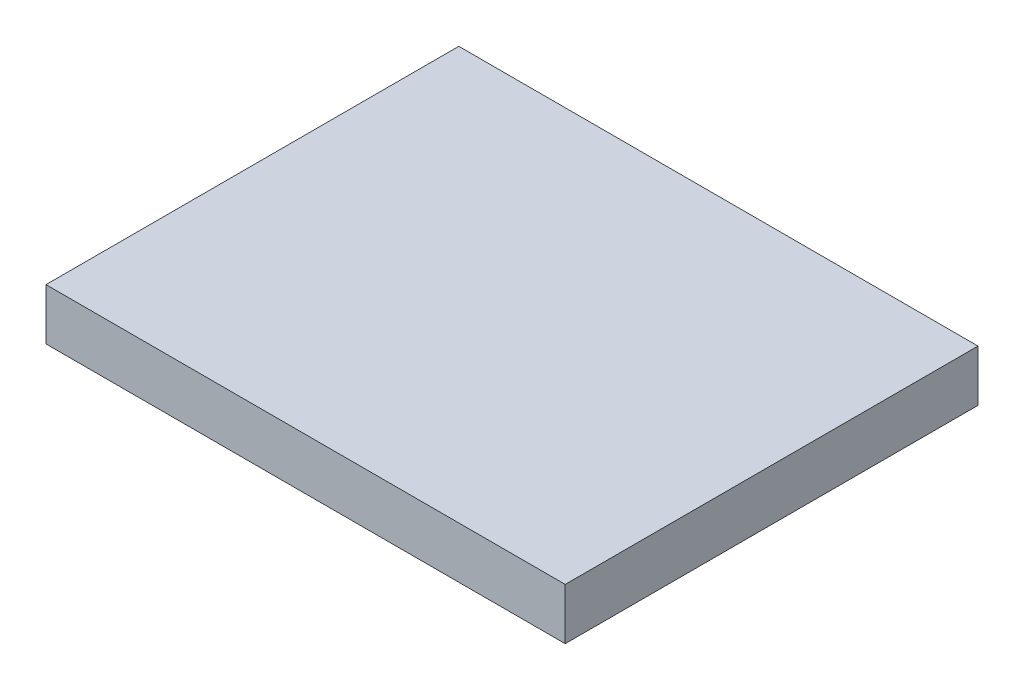
SolidWorks part; units mm, degrees
ref_plane "Front Plane" through (0, 0, 0) normal (0, 0, 1) x (1, 0, 0)
ref_plane "Top Plane" through (0, 0, 0) normal (0, 1, 0) x (1, 0, 0)
ref_plane "Right Plane" through (0, 0, 0) normal (1, 0, 0) x (0, 0, -1)
sketch "Sketch1" plane through (0, 0, 0) normal (0, 1, 0) x (1, 0, 0)
  line L1 (0, 0) -> (283, 0)
  line L2 (0, 0) -> (0, 225)
  line L3 (0, 225) -> (283, 225)
  line L4 (283, 0) -> (283, 225)
  dimension "D1" = 225
  dimension "D2" = 283
extrude "Boss-Extrude1" add sketch "Sketch1" along normal blind 28
sketch "Sketch2" plane through (0, 0, 0) normal (0, -1, 0) x (1, 0, 0)
  line L0 (0, 0) -> (283, 0) construction
  line L1 (283, -225) -> (0, -225) construction
  line L2 (0, -225) -> (0, 0) construction
  line L3 (283, 0) -> (283, -225) construction
  circle A0 centre (25, -25) radius 10
  circle A1 centre (25, -200) radius 10
  circle A2 centre (258, -200) radius 10
  circle A3 centre (258, -25) radius 10
  dimension "D1" = 20
  dimension "D10" = 20
  dimension "D11" = 20
  dimension "D12" = 20
  dimension "D2" = 25
  dimension "D3" = 25
  dimension "D4" = 25
  dimension "D5" = 25
  dimension "D6" = 25
  dimension "D7" = 25
  dimension "D8" = 25
  dimension "D9" = 25
extrude "Boss-Extrude2" add sketch "Sketch2" along normal blind 6.5
equation "\"Length\"= 283mm"
equation "\"Width\"= 225mm"
equation "\"WallThickness\"= 12.5mm"
equation "\"D1@Sketch1\"=\"Width\""
equation "\"D2@Sketch1\"=\"Length\""
equation "\"UpperWaterJacketThickness\"= 28mm"
equation "\"D1@Boss-Extrude1\"=\"UpperWaterJacketThickness\""
equation "\"UpperWaterJacketPegDiameter\"=20"
equation "\"D1@Sketch2\"=\"UpperWaterJacketPegDiameter\""
equation "\"UpperWaterJacketPegDistance\"=2.5"
equation "\"D2@Sketch2\"=\"WallThickness\"+\"UpperWaterJacketPegDiameter\"/2+\"UpperWaterJacketPegDistance\""
equation "\"D3@Sketch2\"=\"WallThickness\"+\"UpperWaterJacketPegDiameter\"/2+\"UpperWaterJacketPegDistance\""
equation "\"D4@Sketch2\"=\"WallThickness\"+\"UpperWaterJacketPegDiameter\"/2+\"UpperWaterJacketPegDistance\""
equation "\"D5@Sketch2\"=\"WallThickness\"+\"UpperWaterJacketPegDiameter\"/2+\"UpperWaterJacketPegDistance\""
equation "\"D6@Sketch2\"=\"WallThickness\"+\"UpperWaterJacketPegDiameter\"/2+\"UpperWaterJacketPegDistance\""
equation "\"D7@Sketch2\"=\"WallThickness\"+\"UpperWaterJacketPegDiameter\"/2+\"UpperWaterJacketPegDistance\""
equation "\"D8@Sketch2\"=\"WallThickness\"+\"UpperWaterJacketPegDiameter\"/2+\"UpperWaterJacketPegDistance\""
equation "\"D9@Sketch2\"=\"WallThickness\"+\"UpperWaterJacketPegDiameter\"/2+\"UpperWaterJacketPegDistance\""
equation "\"D10@Sketch2\"=\"UpperWaterJacketPegDiameter\""
equation "\"D11@Sketch2\"=\"UpperWaterJacketPegDiameter\""
equation "\"D12@Sketch2\"=\"UpperWaterJacketPegDiameter\""
equation "\"UpperWaterJacketPegHeight\"=6.5"
equation "\"D1@Boss-Extrude2\"=\"UpperWaterJacketPegHeight\""
equation "\"SpacerHeight\"= 80.2mm"
equation "\"SpacerCornerWidth\"= 10mm"
equation "\"SpacerCornerHeight\"= 60.16mm"
equation "\"SpacerPegDiameter\"= 10mm"
equation "\"SpacerPegHeight\"= 10mm"
equation "\"TubingShort\"= 110mm"
equation "\"TubingLong\"= 175mm"
equation "\"PlateLength\"= 252mm"
equation "\"PlateWidth\"= 190mm"
equation "\"PlateHoleDiameter\"= 5.9mm"
equation "\"PlateHoleBottom\"= 2mm"
equation "\"PlateHoleSide\"= 1.55mm"
equation "\"PlateHoleSpacing\"= 3.1mm"
equation "\"PlateThickness\"= 1.55mm"
equation "\"ReservoirBottom\"= 12.5mm"
equation "\"ReservoirSupportWidth\"= 12mm"
equation "\"ReservoirSupportHeight\"= 15.1mm"
equation "\"ReservoirSupportPlacementHeight\"= 50mm"
equation "\"ReservoirHoleDiameter\"= 12.7mm"
equation "\"ReservoirHoleRight\"= 25mm"
equation "\"ReservoirHoleTop\"= \"ReservoirSupportPlacementHeight\""
equation "\"ReservoirHeight\"= 90mm"
equation "\"ReservoirPortBottom\"= 4mm"
equation "\"ReservoirPortTop\"= 10mm"
equation "\"ReservoirPortWidth\"= 101mm"
equation "\"CustomSpacerWallThickness\"= 0.375in"
equation "\"CustomSpacerHeight\"= 5in"
equation "\"CustomSpacerRodHoleHeight\"= .75in"
equation "\"CustomSpacerRodHoleDiameter\"= .3125in"
equation "\"ScrewBlockSide\"= 12mm"
equation "\"ScrewBlockUpperHeight\"= 16mm"
equation "\"ScrewBlockLowerHeight\"= 16mm"
equation "\"InternalLength\"= 258mm"
equation "\"InternalWidth\"= 200mm"
